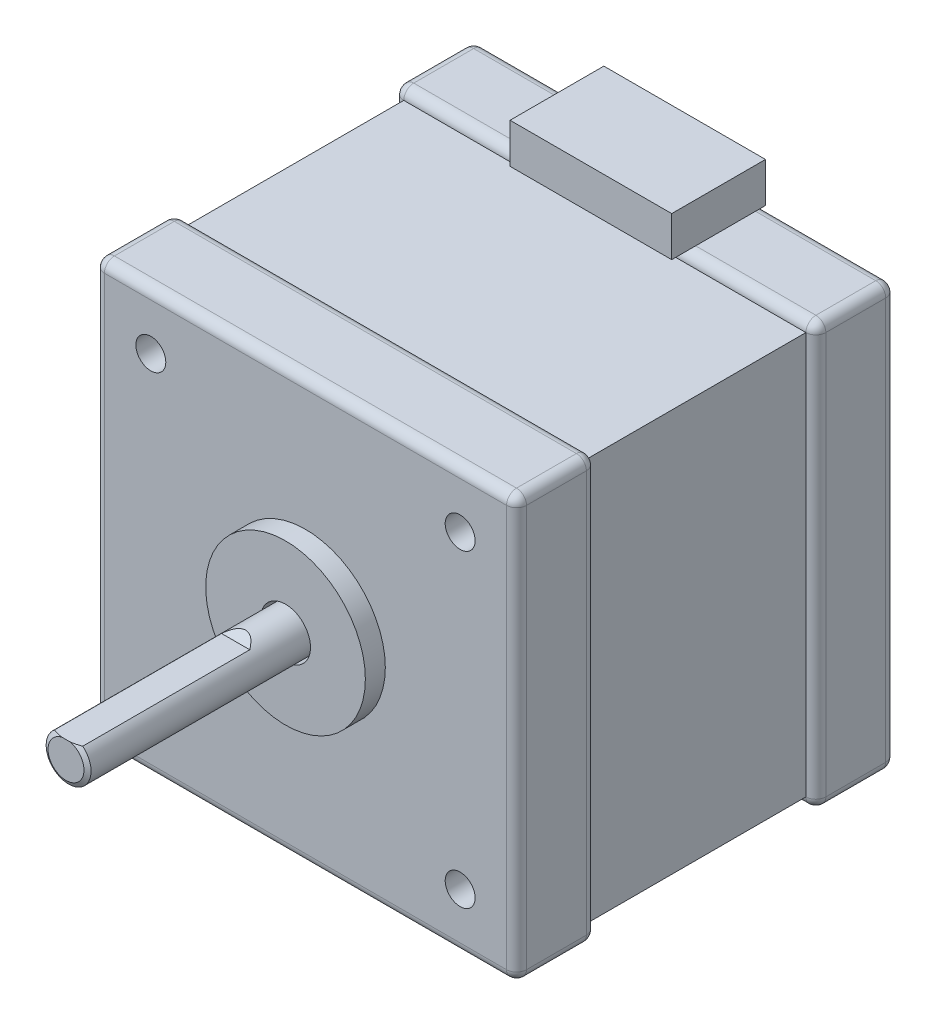
SolidWorks part; units mm, degrees
ref_plane "前视基准面" through (0, 0, 0) normal (0, 0, 1) x (1, 0, 0)
ref_plane "上视基准面" through (0, 0, 0) normal (0, 1, 0) x (1, 0, 0)
ref_plane "右视基准面" through (0, 0, 0) normal (1, 0, 0) x (0, 0, -1)
sketch "草图1" plane through (0, 0, 0) normal (0, 0, 1) x (1, 0, 0)
  line L1 (0, 0) -> (42.3, 0)
  line L2 (0, 0) -> (0, 42.3)
  line L3 (0, 42.3) -> (42.3, 42.3)
  line L4 (42.3, 0) -> (42.3, 42.3)
  dimension "D1" = 42.3
  dimension "D2" = 42.3
extrude "凸台-拉伸1" add sketch "草图1" along normal blind 38
sketch "草图3" plane through (0, 0, 38) normal (0, 0, 1) x (1, 0, 0)
  line L0 (0, 21.15) -> (55.9454, 21.15) construction
  line L1 (0, 42.3) -> (0, 0) construction
  line L2 (21.15, 42.3) -> (21.15, -2.8006) construction
  line L3 (42.3, 42.3) -> (0, 42.3) construction
  line L4 (0, 42.3) -> (42.3, 0) construction
  line L5 (42.3, 0) -> (42.3, 42.3) construction
  line L6 (0, 0) -> (42.3, 0) construction
  line L7 (42.3, 42.3) -> (-0.1224, -0.1224) construction
  line L8 (5.65, 36.65) -> (36.65, 36.65) construction
  circle A0 centre (5.65, 36.65) radius 1.5
  circle A1 centre (36.65, 36.65) radius 1.5
  circle A2 centre (36.65, 5.65) radius 1.5
  circle A3 centre (5.65, 5.65) radius 1.5
  dimension "D1" = 3
  dimension "D2" = 3
  dimension "D3" = 31
extrude "切除-拉伸1" cut sketch "草图3" against normal blind 4.5
sketch "草图4" plane through (0, 0, 38) normal (0, 0, 1) x (1, 0, 0)
  line L4 (0, 42.3) -> (0, 0)
  line L5 (0, 0) -> (42.3, 0)
  line L6 (42.3, 0) -> (42.3, 42.3)
  line L7 (42.3, 42.3) -> (0, 42.3)
  line L8 (0, 42.3) -> (0, 0) construction
  line L9 (0, 0) -> (42.3, 0) construction
  line L10 (42.3, 0) -> (42.3, 42.3) construction
  line L11 (42.3, 42.3) -> (0, 42.3) construction
  circle A0 centre (21.15, 21.15) radius 8
  circle A1 centre (21.15, 21.15) radius 2.5
  dimension "D2" = 16
  dimension "D3" = 5
  dimension "D1" = 0
extrude "凸台-拉伸2" add sketch "草图4" along normal blind 2
sketch "草图5" plane through (0, 0, 38) normal (0, 0, 1) x (1, 0, 0)
  circle A0 centre (21.15, 21.15) radius 2.25
  dimension "D1" = 4.5
extrude "凸台-拉伸3" add sketch "草图5" along normal blind 24
sketch "草图6" plane through (0, 0, 0) normal (1, 0, 0) x (0, 0, -1)
  line L0 (-62, 22.9) -> (-45, 22.9)
  line L1 (-62, 23.4) -> (-62, 18.9) construction
  line L2 (-45, 22.9) -> (-44, 23.4)
  line L3 (-38, 23.4) -> (-62, 23.4) construction
  line L4 (-62, 22.9) -> (-62, 23.4)
  line L5 (-62, 23.4) -> (-44, 23.4)
  dimension "D1" = 18
  dimension "D2" = 17
  dimension "D3" = 0.5
extrude "切除-拉伸2" cut sketch "草图6" along normal blind 24
ref_plane "基准面1" through (0, 21.15, 0) normal (0, 1, 0) x (1, 0, 0)
sketch "草图9" plane through (0, 21.15, 0) normal (0, 1, 0) x (1, 0, 0)
  line L0 (21.15, -62) -> (21.15, -61.4763)
  line L1 (22.5642, -62) -> (19.7358, -62) construction
  line L3 (23.4, -62) -> (23.4, -38) construction
  line L4 (23.4, -61.7394) -> (22.6, -62.2012)
  line L5 (22.6, -62.2012) -> (23.4, -62.2012)
  line L6 (23.4, -62.2012) -> (23.4, -61.7394)
  point P4 (23.4, -61.7057)
  point P11 (23.3951, -61.4794)
  dimension "D1" = 30
  dimension "D2" = 0.8
revolve "切除-旋转1" cut sketch "草图9" angle 360 about L0 region at (23.1333, 21.15, 62.0473)
fillet "圆角1" radius 1 12 edges at (0, 21.15, 0) (21.15, 42.3, 0) (0, 42.3, 19) (21.15, 42.3, 38) (42.3, 21.15, 38) (0, 0, 19) (21.15, 0, 38) (21.15, 0, 0) (42.3, 21.15, 0) (42.3, 42.3, 19) (42.3, 0, 19) (0, 21.15, 38)
sketch "草图10" plane through (0, 0, 38) normal (0, 0, 1) x (1, 0, 0)
  line L1 (0, 42.3) -> (42.3, 42.3)
  line L2 (0, 42.3) -> (0, 0)
  line L3 (0, 0) -> (42.3, 0)
  line L4 (41.3, 41.3) -> (1, 41.3)
  line L5 (1, 41.3) -> (1, 1)
  line L6 (1, 1) -> (41.3, 1)
  line L7 (41.3, 1) -> (41.3, 41.3)
  line L8 (41.3, 41.3) -> (1, 41.3)
  line L9 (1, 41.3) -> (1, 1)
  line L10 (1, 1) -> (41.3, 1)
  line L11 (41.3, 1) -> (41.3, 41.3)
  line L12 (42.3, 42.3) -> (42.3, 0)
  dimension "D1" = 0
extrude "切除-拉伸4" cut sketch "草图10" against normal blind 22 from offset 8 offset against normal yes
fillet "圆角2" radius 1 16 edges at (0.2929, 42.0071, 8) (21.15, 42.3, 8) (42.0071, 42.0071, 8) (42.3, 21.15, 8) (42.0071, 0.2929, 8) (21.15, 0, 8) (0.2929, 0.2929, 8) (0.2929, 42.0071, 30) (21.15, 42.3, 30) (42.0071, 42.0071, 30) (42.3, 21.15, 30) (42.0071, 0.2929, 30) (21.15, 0, 30) (0.2929, 0.2929, 30) (0, 21.15, 8) (0, 21.15, 30)
sketch "草图11" plane through (0, 42.3, 0) normal (0, 1, 0) x (1, 0, 0)
  line L0 (21.15, 0) -> (21.15, -4.6085) construction
  line L2 (13.05, 0) -> (13.05, -9.4)
  line L3 (1, 0) -> (41.3, 0) construction
  line L4 (13.05, -9.4) -> (29.25, -9.4)
  line L5 (29.25, 0) -> (29.25, -9.4)
  line L6 (13.05, 0) -> (29.25, 0)
  point P8 (21.15, -9.4)
  dimension "D1" = 9.4
  dimension "D2" = 8.1
extrude "凸台-拉伸4" add sketch "草图11" along normal blind 4
